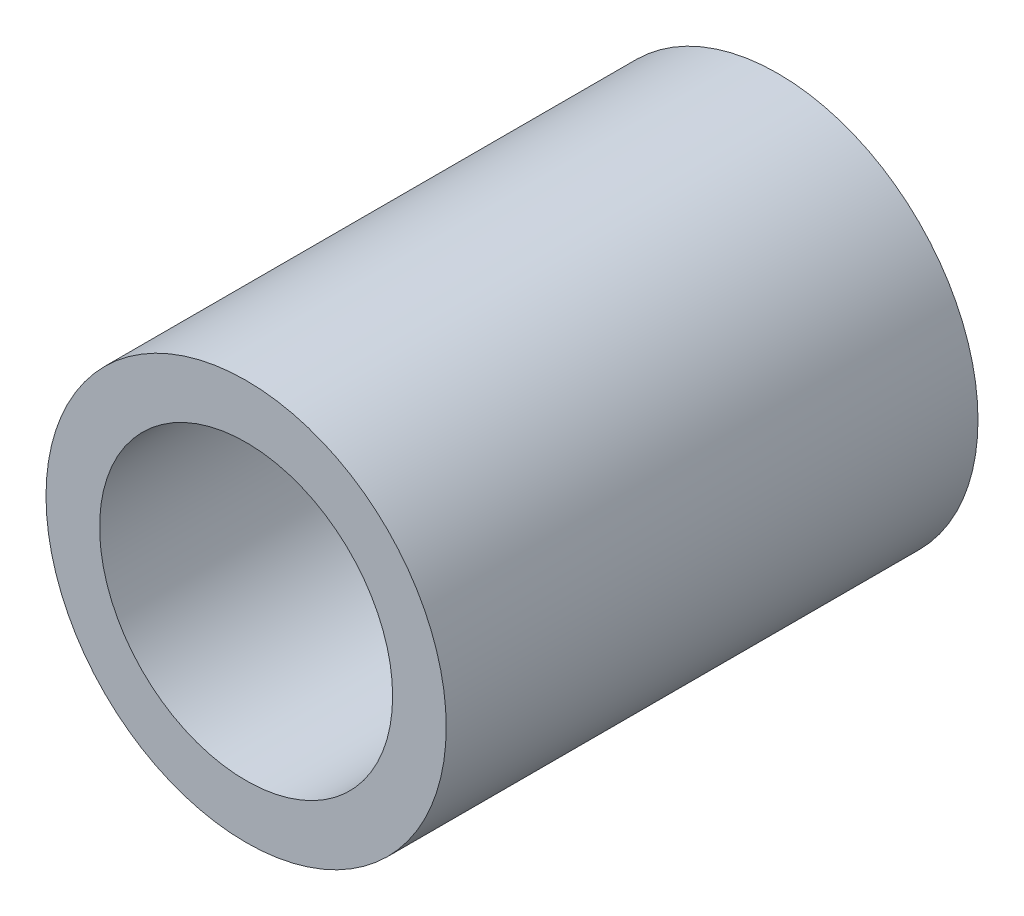
SolidWorks part; units mm, degrees
material "PLA 50%"
ref_plane "Front Plane" through (0, 0, 0) normal (0, 0, 1) x (1, 0, 0)
ref_plane "Top Plane" through (0, 0, 0) normal (0, 1, 0) x (1, 0, 0)
ref_plane "Right Plane" through (0, 0, 0) normal (1, 0, 0) x (0, 0, -1)
ref_axis "X" through (-88.99, 0, 0) along (1, 0, 0)
ref_axis "Y" through (0, 55, 0) along (0, -1, 0)
ref_axis "Z" through (0, 0, -88.99) along (0, 0, 1)
sketch "Sketch1" plane through (0, 0, 0) normal (0, 0, 1) x (1, 0, 0)
  circle A0 centre (0, 0) radius 5.125
  circle A1 centre (0, 0) radius 7
  dimension "D1" = 10.25
  dimension "D2" = 14
extrude "Boss-Extrude1" add sketch "Sketch1" against normal up to surface (18.6012 mm away)
